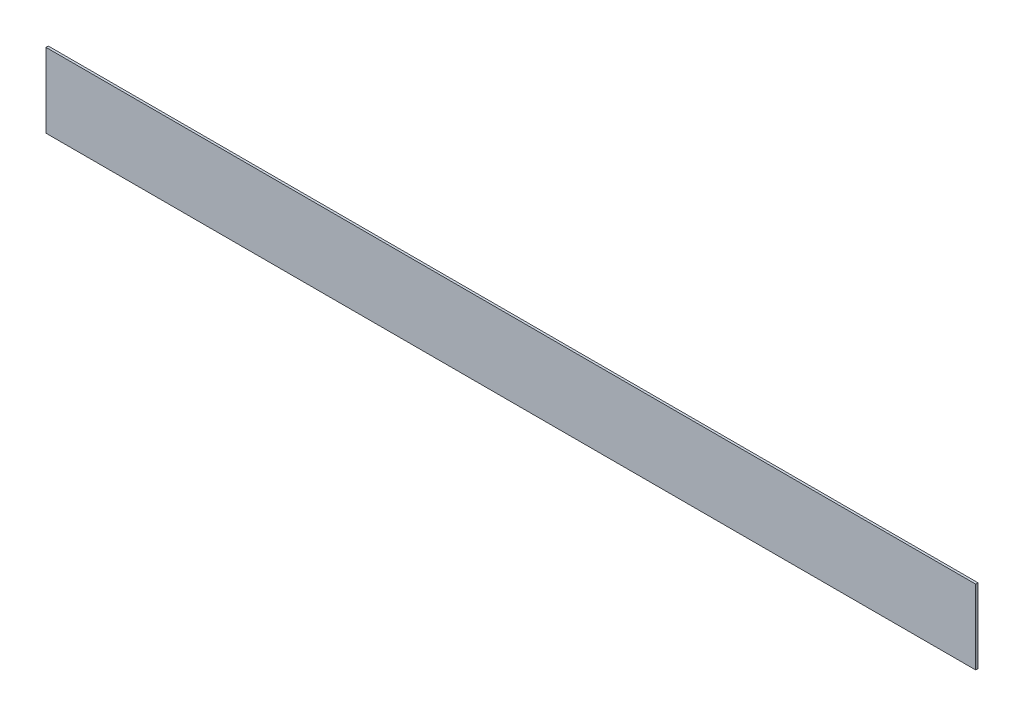
SolidWorks part; units mm, degrees
ref_plane "Front Plane" through (0, 0, 0) normal (0, 0, 1) x (1, 0, 0)
ref_plane "Top Plane" through (0, 0, 0) normal (0, 1, 0) x (1, 0, 0)
ref_plane "Right Plane" through (0, 0, 0) normal (1, 0, 0) x (0, 0, -1)
sketch "Sketch1" plane through (0, 0, 0) normal (0, 0, 1) x (1, 0, 0)
  line L1 (0, 0) -> (635, 0)
  line L2 (0, 0) -> (0, 50.8)
  line L3 (0, 50.8) -> (635, 50.8)
  line L4 (635, 0) -> (635, 50.8)
  dimension "D1" = 50.8
  dimension "D2" = 635
extrude "Boss-Extrude1" add sketch "Sketch1" along normal blind 1.5875
